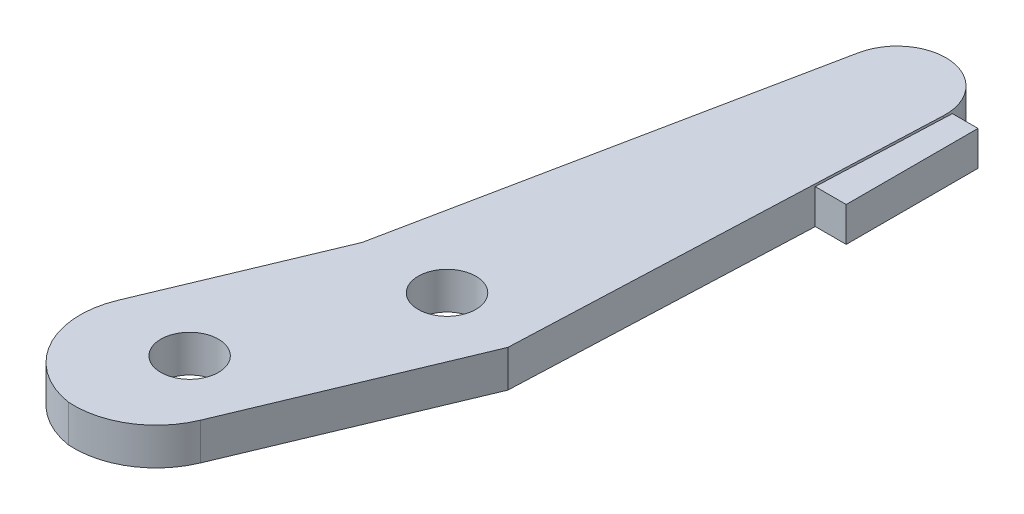
SolidWorks part; units mm, degrees
ref_plane "Front Plane" through (0, 0, 0) normal (0, 0, 1) x (1, 0, 0)
ref_plane "Top Plane" through (0, 0, 0) normal (0, 1, 0) x (1, 0, 0)
ref_plane "Right Plane" through (0, 0, 0) normal (1, 0, 0) x (0, 0, -1)
sketch "Sketch1" plane through (0, 0, 0) normal (0, 1, 0) x (1, 0, 0)
  line L0 (0, 0) -> (6.9428, 16.6071)
  line L1 (6.9428, 16.6071) -> (12.5242, 44.0452)
  line L6 (16.883, 15.5144) -> (9.9401, -1.0927)
  line L7 (9.9401, -1.0927) -> (0, 0)
  line L9 (16.883, 15.5144) -> (18.0532, 44.0452)
  line L10 (18.0532, 44.0452) -> (12.5242, 44.0452)
  point P2 (10.9548, 43.8019)
  point P6 (17.6857, 43.5626)
  point P7 (10.853, 43.1801)
  point P10 (16.4675, 43.2891)
  point P11 (0, 0)
  point P12 (0, 0)
  point P13 (0, 0)
  point P14 (0, 0)
  point P15 (0, 0)
  point P16 (12.0162, 43.1777)
  point P17 (0, 0)
  point P18 (0, 0)
  point P19 (18.2083, 43.2744)
  point P20 (0, 0)
  point P21 (0, 0)
  point P22 (12.7902, 43.1777)
  point P23 (16.2555, 15.763)
  point P24 (0, 0)
  point P25 (0, 0)
  point P26 (6.9428, 16.6071)
  point P27 (0, 0)
  point P28 (0, 0)
  point P29 (0, 0)
  point P30 (0, 0)
  dimension "D1" = 10
  dimension "D2" = 18
  dimension "D3" = 18
  dimension "D4" = 28
extrude "Boss-Extrude1" add sketch "Sketch1" along normal blind 2.25
fillet "Fillet1" radius 5 2 edges at (9.9401, 1.125, 1.0927) (0, 1.125, 0)
fillet "Fillet2" radius 3 2 edges at (12.5242, 1.125, -44.0452) (18.0532, 1.125, -44.0452)
sketch "Sketch2" plane through (0, 2.25, 0) normal (0, 1, 0) x (1, 0, 0)
  circle A0 centre (7.6677, 5.4139) radius 1.75
  circle A1 centre (12.17, 16.5373) radius 1.75
  dimension "D1" = 3.5
  dimension "D2" = 3.5
  dimension "D3" = 12
extrude "Cut-Extrude1" cut sketch "Sketch2" against normal through all
ref_plane "Plane1" through (19.5, 0, 0) normal (1, 0, 0) x (0, 0, -1)
sketch "Sketch4" plane through (19.5, -1.4847, -8.2019) normal (1, 0, 0) x (0, 0, -1)
  line L1 (33.2372, 3.5919) -> (25.2372, 3.5919)
  line L2 (33.2372, 3.5919) -> (33.2372, 1.4919)
  line L3 (33.2372, 1.4919) -> (25.2372, 1.4919)
  line L4 (25.2372, 3.5919) -> (25.2372, 1.4919)
  dimension "D1" = 2.1
  dimension "D2" = 8
extrude "Boss-Extrude2" add sketch "Sketch4" against normal up to surface (1.5537 mm away) up to face at (17.404, 1.125, -28.2184)
extrude "Boss-Extrude3" add sketch "Sketch4<2>" against normal up to surface (1.5537 mm away) up to face at (17.5878, 1.0911, -32.6995)
sketch "Sketch4<2>" plane through (19.5, -1.4847, -8.2019) normal (1, 0, 0) x (0, 0, -1) same geometry as "Sketch4"
